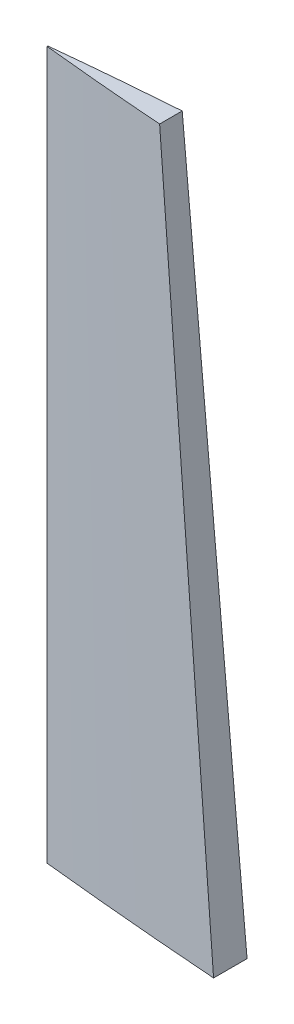
SolidWorks part; units mm, degrees
ref_plane "Front Plane" through (0, 0, 0) normal (0, 0, 1) x (1, 0, 0)
ref_plane "Top Plane" through (0, 0, 0) normal (0, 1, 0) x (1, 0, 0)
ref_plane "Right Plane" through (0, 0, 0) normal (1, 0, 0) x (0, 0, -1)
ref_plane "Plane1" through (0, 22, 0) normal (0, 1, 0) x (1, 0, 0)
sketch "Sketch1" plane through (0, 22, 0) normal (0, 1, 0) x (1, 0, 0)
  line L0 (-118.1355, 4.3944) -> (-118.1355, -4.3944)
  line L1 (-166.125, 0.1512) -> (-166.125, -0.1512)
  spline S0 degree 3 poles (-118.1355, 4.3944) (-118.3151, 4.3817) (-120.9821, 4.1936) (-125.9888, 3.8058) (-132.9846, 3.2473) (-139.4668, 2.6989) (-145.3649, 2.1776) (-150.6142, 1.6942) (-155.157, 1.2607) (-158.9437, 0.8879) (-161.9328, 0.5862) (-164.0916, 0.3639) (-165.3964, 0.2278) (-165.979, 0.1665) (-166.125, 0.1512) knots 0 0 0 0 0.011212 0.166483 0.312686 0.448211 0.571563 0.681381 0.776452 0.855723 0.918312 0.963525 0.990856 1 1 1 1
  spline S1 degree 3 poles (-118.1355, -4.3944) (-118.3151, -4.3817) (-120.9821, -4.1936) (-125.9888, -3.8058) (-132.9846, -3.2473) (-139.4668, -2.6989) (-145.3649, -2.1776) (-150.6142, -1.6942) (-155.157, -1.2607) (-158.9437, -0.8879) (-161.9328, -0.5862) (-164.0916, -0.3639) (-165.3964, -0.2278) (-165.979, -0.1665) (-166.125, -0.1512) knots 0 0 0 0 0.011212 0.166483 0.312686 0.448211 0.571563 0.681381 0.776452 0.855723 0.918312 0.963525 0.990856 1 1 1 1
ref_plane "Plane2" through (0, 207.656, 0) normal (0, 1, 0) x (1, 0, 0)
sketch "Sketch2" plane through (0, 207.656, 0) normal (0, 1, 0) x (1, 0, 0)
  line L0 (-133.7306, 2.9664) -> (-133.7306, -2.9664)
  line L1 (-166.125, 0.102) -> (-166.125, -0.102)
  spline S0 degree 3 poles (-133.7306, 2.9664) (-133.8519, 2.9578) (-135.6522, 2.8308) (-139.0318, 2.569) (-143.7542, 2.192) (-148.1299, 1.8218) (-152.1113, 1.4699) (-155.6547, 1.1436) (-158.7213, 0.851) (-161.2774, 0.5994) (-163.2952, 0.3957) (-164.7524, 0.2456) (-165.6332, 0.1537) (-166.0264, 0.1124) (-166.125, 0.102) knots 0 0 0 0 0.011212 0.166483 0.312686 0.448211 0.571563 0.681381 0.776452 0.855723 0.918312 0.963525 0.990856 1 1 1 1
  spline S1 degree 3 poles (-133.7306, -2.9664) (-133.8519, -2.9578) (-135.6522, -2.8308) (-139.0318, -2.569) (-143.7542, -2.192) (-148.1299, -1.8218) (-152.1113, -1.4699) (-155.6547, -1.1436) (-158.7213, -0.851) (-161.2774, -0.5994) (-163.2952, -0.3957) (-164.7524, -0.2456) (-165.6332, -0.1537) (-166.0264, -0.1124) (-166.125, -0.102) knots 0 0 0 0 0.011212 0.166483 0.312686 0.448211 0.571563 0.681381 0.776452 0.855723 0.918312 0.963525 0.990856 1 1 1 1
loft "Loft1" add profiles "Sketch1", "Sketch2" connector at (-118.1355, 22, -4.3944) connector at (-133.7306, 207.656, -2.9664)
